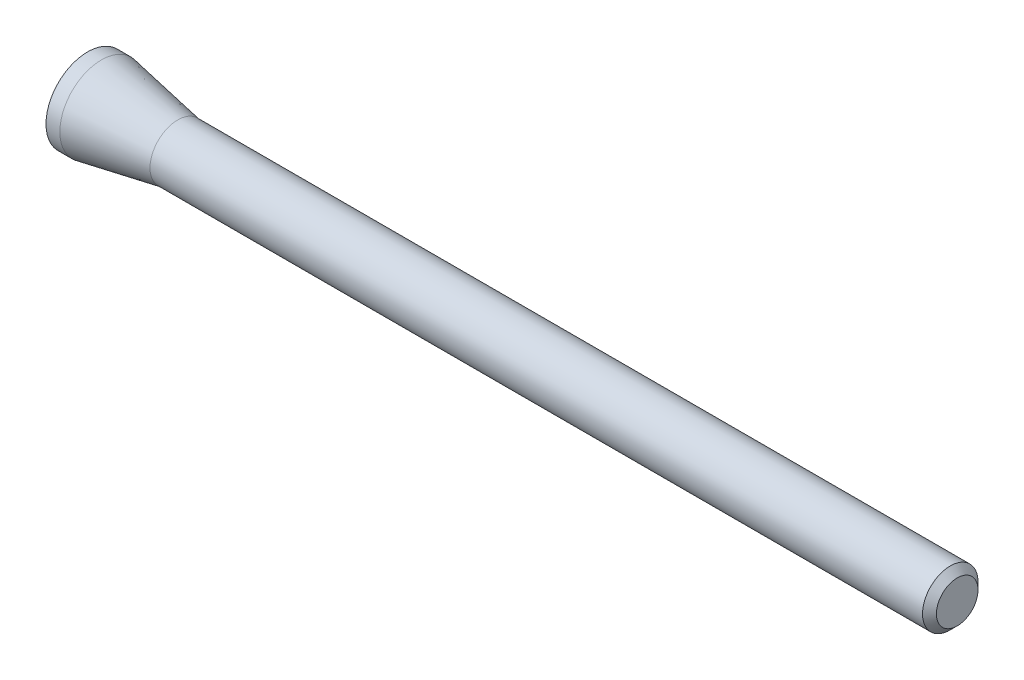
SolidWorks part; units mm, degrees
material "Brass"
ref_plane "Front Plane" through (0, 0, 0) normal (0, 0, 1) x (1, 0, 0)
ref_plane "Top Plane" through (0, 0, 0) normal (0, 1, 0) x (1, 0, 0)
ref_plane "Right Plane" through (0, 0, 0) normal (1, 0, 0) x (0, 0, -1)
sketch "Sketch1" plane through (0, 0, 0) normal (0, 0, 1) x (1, 0, 0)
  line L0 (0, 0) -> (0, 3)
  line L1 (0, 3) -> (1, 3)
  line L2 (1, 3) -> (6.5, 2)
  line L3 (6.5, 2) -> (62.7, 2)
  line L4 (62.7, 2) -> (62.7, 0)
  line L5 (-7.5979, 0) -> (69.3857, 0) construction
  line L6 (0, 0) -> (62.7, 0)
  dimension "D1" = 2
  dimension "D2" = 62.7
  dimension "D3" = 3
  dimension "D4" = 1
  dimension "D5" = 5.5
revolve "Revolve1" add sketch "Sketch1" angle 360 about L5
sketch "Sketch2" plane through (62.7, 0, 0) normal (1, 0, 0) x (0, 0, -1)
  point P0 (0, 0)
sketch "Sketch4" plane through (0, 0, 0) normal (-1, 0, 0) x (0, 0, 1)
  point P0 (0, 0)
ref_axis "Axis1" through (0, 0, 0) along (1, 0, 0)
chamfer "Chamfer1" distance 0.5 angle 45 1 edges at (62.7, 0, 2)
